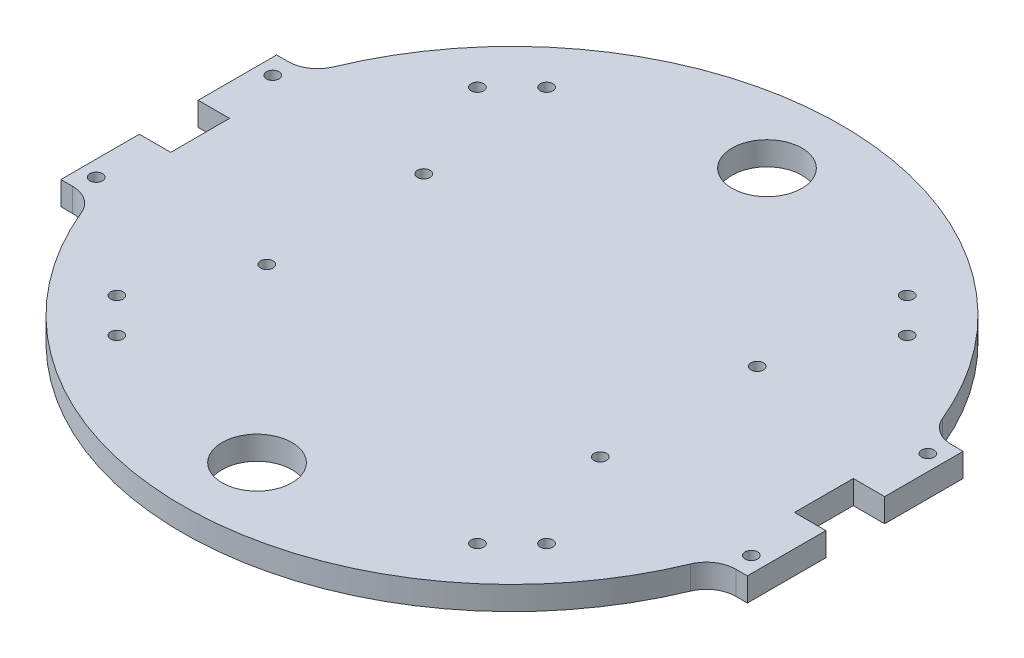
SolidWorks part; units mm, degrees
ref_plane "Plan de face" through (0, 0, 0) normal (0, 0, 1) x (1, 0, 0)
ref_plane "Plan de dessus" through (0, 0, 0) normal (0, 1, 0) x (1, 0, 0)
ref_plane "Plan de droite" through (0, 0, 0) normal (1, 0, 0) x (0, 0, -1)
sketch "Esquisse1" plane through (0, 0, 0) normal (0, 1, 0) x (1, 0, 0)
  line L0 (-87.5, 27.5) -> (-79.371, 27.5)
  line L1 (-87.5, 0) -> (85, 0) construction
  line L2 (-87.5, -27.5) -> (87.5, -27.5) construction
  line L3 (-87.5, -27.5) -> (-87.5, 27.5) construction
  line L4 (0, 84) -> (0, -84) construction
  line L5 (-87.5, 27.5) -> (87.5, 27.5) construction
  line L6 (87.5, -27.5) -> (87.5, 27.5) construction
  line L7 (-87.5, -27.5) -> (-79.371, -27.5)
  line L8 (87.5, -27.5) -> (79.371, -27.5)
  line L9 (87.5, 27.5) -> (79.371, 27.5)
  line L10 (0, 0) -> (-54.7722, 45.9593) construction
  line L11 (0, 0) -> (-45.9593, 54.7722) construction
  line L12 (-87.5, 27.5) -> (-87.5, 7.5)
  line L13 (-87.5, 7.5) -> (-79.5, 7.5)
  line L14 (-79.5, 7.5) -> (-79.5, -7.5)
  line L15 (-79.5, -7.5) -> (-87.5, -7.5)
  line L16 (-87.5, -7.5) -> (-87.5, -27.5)
  line L17 (87.5, -27.5) -> (87.5, -7.5)
  line L18 (79.5, -7.5) -> (87.5, -7.5)
  line L19 (79.5, 7.5) -> (79.5, -7.5)
  line L20 (87.5, 7.5) -> (79.5, 7.5)
  line L21 (87.5, 27.5) -> (87.5, 7.5)
  circle A0 centre (0, 0) radius 84 construction
  arc A1 (79.371, 27.5) -> (-79.371, 27.5) centre (0, 0) ccw
  arc A2 (-79.371, -27.5) -> (79.371, -27.5) centre (0, 0) ccw
  circle A3 centre (0, 0) radius 71.5 construction
  circle A4 centre (-54.7722, 45.9593) radius 1.6
  circle A5 centre (-45.9593, 54.7722) radius 1.6
  circle A6 centre (54.7722, 45.9593) radius 1.6
  circle A7 centre (45.9593, 54.7722) radius 1.6
  circle A8 centre (45.9593, -54.7722) radius 1.6
  circle A9 centre (54.7722, -45.9593) radius 1.6
  circle A10 centre (-54.7722, -45.9593) radius 1.6
  circle A11 centre (-45.9593, -54.7722) radius 1.6
  circle A12 centre (0, 65) radius 8.9
  circle A13 centre (0, -65) radius 8.9
  circle A14 centre (-83.5, 22.5) radius 1.6
  circle A15 centre (-83.5, -22.5) radius 1.6
  circle A16 centre (-42.5, 20) radius 1.6
  circle A17 centre (-42.5, -20) radius 1.6
  circle A18 centre (42.5, -20) radius 1.6
  circle A19 centre (42.5, 20) radius 1.6
  circle A24 centre (83.5, -22.5) radius 1.6
  circle A25 centre (83.5, 22.5) radius 1.6
  point P35 (0, 0)
  dimension "D1" = 168
  dimension "D6" = 10
  dimension "D5" = 40
  dimension "D8" = 65
  dimension "D9" = 22.5
  dimension "D12" = 45
  dimension "D11" = 20
  dimension "D2" = 87.5
  dimension "D3" = 175
  dimension "D4" = 55
  dimension "D13" = 7.5
  dimension "D14" = 15
  dimension "D15" = 8
  dimension "D7" = 4
extrude "Boss.-Extru.1" add sketch "Esquisse1" along normal blind 6
fillet "Congé1" radius 7.5 4 edges at (-79.371, 3, 27.5) (-79.371, 3, -27.5) (79.371, 3, -27.5) (79.371, 3, 27.5)
